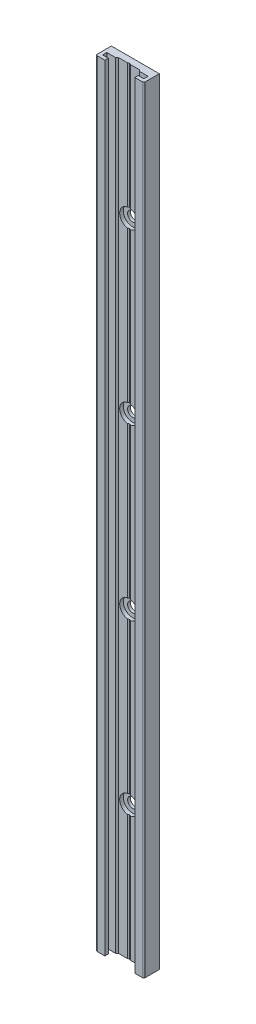
SolidWorks part; units mm, degrees
ref_plane "Front Plane" through (0, 0, 0) normal (0, 0, 1) x (1, 0, 0)
ref_plane "Top Plane" through (0, 0, 0) normal (0, 1, 0) x (1, 0, 0)
ref_plane "Right Plane" through (0, 0, 0) normal (1, 0, 0) x (0, 0, -1)
ref_plane "Plane1" through (0, 137.5, 0) normal (0, 1, 0) x (1, 0, 0)
sketch "Sketch1" plane through (0, 137.5, 0) normal (0, 1, 0) x (1, 0, 0)
  line L0 (-8.5, 0) -> (-8.5, -5)
  line L1 (-8, -5.5) -> (-5.3, -5.5)
  line L2 (-5.3, -5.5) -> (-5.3, -4.3)
  line L3 (-5.3, -4.3) -> (-7.3, -4.3)
  line L4 (-7.3, -4.3) -> (-7.3, -2.8)
  line L5 (-7.3, -2.8) -> (-4.25, -2.8)
  line L6 (-4.25, -2.8) -> (-3.75, -2.3)
  line L7 (-3.75, -2.3) -> (-0.5, -2.3)
  line L8 (-0.5, -2.3) -> (0, -2.0113)
  line L9 (0, -2.0113) -> (0.5, -2.3)
  line L10 (0.5, -2.3) -> (3.75, -2.3)
  line L11 (3.75, -2.3) -> (4.25, -2.8)
  line L12 (4.25, -2.8) -> (7.3, -2.8)
  line L13 (7.3, -2.8) -> (7.3, -4.3)
  line L14 (7.3, -4.3) -> (5.3, -4.3)
  line L15 (5.3, -4.3) -> (5.3, -5.5)
  line L16 (5.3, -5.5) -> (8, -5.5)
  line L17 (8.5, -5) -> (8.5, 0)
  line L18 (8.5, 0) -> (-8.5, 0)
  arc A0 (-8.5, -5) -> (-8, -5.5) centre (-8, -5) ccw
  arc A1 (8, -5.5) -> (8.5, -5) centre (8, -5) ccw
extrude "Boss-Extrude1" add sketch "Sketch1" against normal blind 275
ref_plane "Plane2" through (0, -90, 0) normal (0, 1, 0) x (1, 0, 0)
sketch "Sketch2" plane through (0, -90, 0) normal (0, 1, 0) x (1, 0, 0)
  line L0 (1.75, 0) -> (0, 0)
  line L1 (0, 0) -> (0, -2.3)
  line L2 (0, -2.3) -> (3.25, -2.3)
  line L3 (3.25, -2.3) -> (3.25, -1)
  line L4 (3.25, -1) -> (1.75, -1)
  line L5 (1.75, -1) -> (1.75, 0)
  line L6 (0, 0) -> (0, -2.3) construction
revolve "Cut-Revolve1" cut sketch "Sketch2" angle 360 about L6 reverse direction yes
sketch3d "3DSketch1"
  point P0 (0, 0.3115, 1.941)
  point P1 (0, 100.3115, 1.941)
ref_axis "Axis1" through (0, 0.3115, 1.941) along (0, 1, 0)
pattern_linear "LPattern1" count 4 spacing 60 along (0, 1, 0) of "Cut-Revolve1"
ref_axis "Axis2" through (0, 90, 0) along (0, 0, 1)
ref_axis "Axis3" through (0, 30, 0) along (0, 0, 1)
ref_axis "Axis4" through (0, -30, 0) along (0, 0, 1)
ref_axis "Axis5" through (0, -90, 0) along (0, 0, 1)
ref_plane "Plane3" through (0, 0, 0) normal (1, 0, 0) x (0, 0, -1)
ref_plane "Plane4" through (0, 0, 0) normal (0, 1, 0) x (1, 0, 0)
